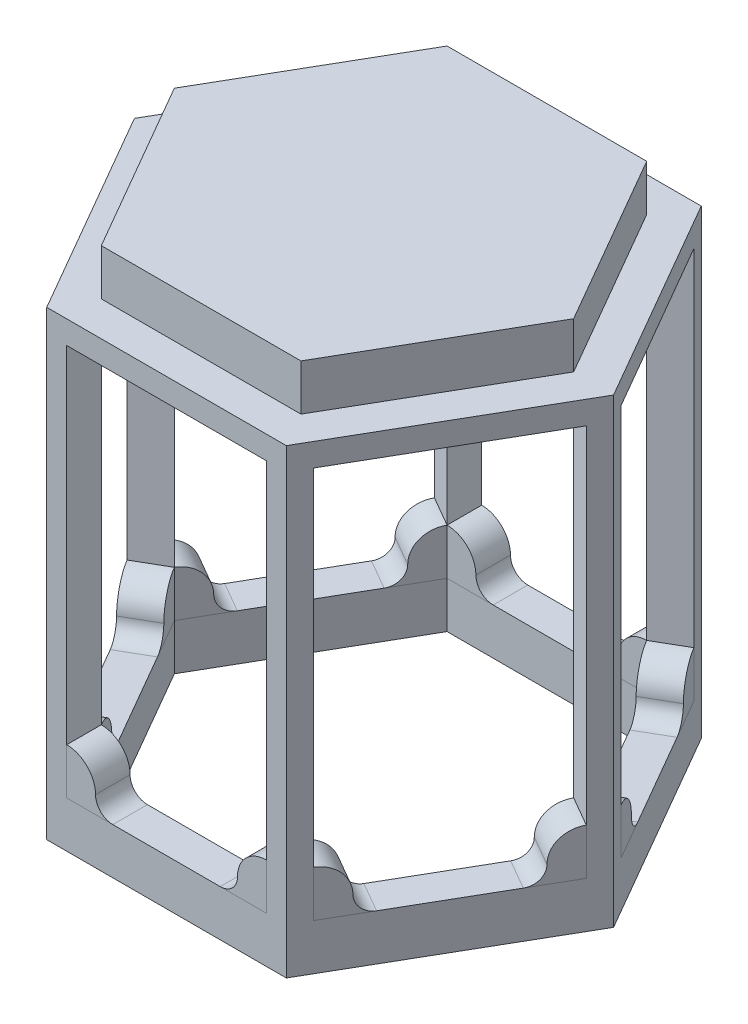
SolidWorks part; units mm, degrees
ref_plane "Front Plane" through (0, 0, 0) normal (0, 0, 1) x (1, 0, 0)
ref_plane "Top Plane" through (0, 0, 0) normal (0, 1, 0) x (1, 0, 0)
ref_plane "Right Plane" through (0, 0, 0) normal (1, 0, 0) x (0, 0, -1)
sketch "Sketch1" plane through (0, 0, 0) normal (0, 1, 0) x (1, 0, 0)
  line L1 (8.6603, 0) -> (4.3301, 7.5)
  line L2 (4.3301, 7.5) -> (-4.3301, 7.5)
  line L3 (-4.3301, 7.5) -> (-8.6603, 0)
  line L4 (-8.6603, 0) -> (-4.3301, -7.5)
  line L5 (-4.3301, -7.5) -> (4.3301, -7.5)
  line L6 (4.3301, -7.5) -> (8.6603, 0)
  line L7 (10.3923, 0) -> (5.1962, 9)
  line L8 (5.1962, 9) -> (-5.1962, 9)
  line L9 (-5.1962, 9) -> (-10.3923, 0)
  line L10 (-10.3923, 0) -> (-5.1962, -9)
  line L11 (-5.1962, -9) -> (5.1962, -9)
  line L12 (5.1962, -9) -> (10.3923, 0)
  circle A0 centre (0, 0) radius 7.5 construction
  circle A1 centre (0, 0) radius 9 construction
  dimension "D1" = 15
  dimension "D2" = 1.5
extrude "Boss-Extrude1" add sketch "Sketch1" along normal blind 2
sketch "Sketch2" plane through (0, 2, 0) normal (0, 1, 0) x (1, 0, 0)
  line L0 (-5.1962, 9) -> (-5.6292, 8.25)
  line L1 (-5.1962, 9) -> (-10.3923, 0) construction
  line L5 (-5.1962, 9) -> (-4.3301, 7.5) construction
  line L39 (-4.3301, 7.5) -> (-5.6292, 8.25)
  line L40 (-4.3301, 7.5) -> (-4.3301, 9)
  line L41 (-5.1962, 9) -> (-4.3301, 9)
  line L42 (4.3301, 7.5) -> (5.6292, 8.25)
  line L43 (5.1962, 9) -> (5.6292, 8.25)
  line L44 (5.1962, 9) -> (4.3301, 9)
  line L45 (4.3301, 7.5) -> (4.3301, 9)
  line L46 (8.6603, 0) -> (9.9593, -0.75)
  line L47 (10.3923, 0) -> (9.9593, -0.75)
  line L48 (10.3923, 0) -> (9.9593, 0.75)
  line L49 (8.6603, 0) -> (9.9593, 0.75)
  line L50 (4.3301, -7.5) -> (4.3301, -9)
  line L51 (5.1962, -9) -> (4.3301, -9)
  line L52 (5.1962, -9) -> (5.6292, -8.25)
  line L53 (4.3301, -7.5) -> (5.6292, -8.25)
  line L54 (-4.3301, -7.5) -> (-5.6292, -8.25)
  line L55 (-5.1962, -9) -> (-5.6292, -8.25)
  line L56 (-5.1962, -9) -> (-4.3301, -9)
  line L57 (-4.3301, -7.5) -> (-4.3301, -9)
  line L58 (-8.6603, 0) -> (-9.9593, 0.75)
  line L59 (-10.3923, 0) -> (-9.9593, 0.75)
  line L60 (-10.3923, 0) -> (-9.9593, -0.75)
  line L61 (-8.6603, 0) -> (-9.9593, -0.75)
  line L62 (-4.3301, 7.5) -> (-8.6603, 0) construction
  point P7 (-0.7978, -1.0505)
  point P30 (0, 0)
  dimension "D1" = 90
  dimension "D2" = 6
extrude "Boss-Extrude2" add sketch "Sketch2" along normal blind 17
sketch "Sketch3" plane through (0, 19, 0) normal (0, 1, 0) x (1, 0, 0)
  line L1 (10.3923, 0) -> (5.1962, 9)
  line L2 (5.1962, 9) -> (-5.1962, 9)
  line L3 (-5.1962, 9) -> (-10.3923, 0)
  line L4 (-10.3923, 0) -> (-5.1962, -9)
  line L5 (-5.1962, -9) -> (5.1962, -9)
  line L6 (5.1962, -9) -> (10.3923, 0)
  circle A0 centre (0, 0) radius 9 construction
  point P1 (10.3923, 0)
extrude "Boss-Extrude3" add sketch "Sketch3" along normal blind 1
sketch "Sketch4" plane through (0, 20, 0) normal (0, 1, 0) x (1, 0, 0)
  line L0 (10.3923, 0) -> (5.1962, 9) construction
  line L1 (8.6603, 0) -> (4.3301, 7.5)
  line L2 (4.3301, 7.5) -> (-4.3301, 7.5)
  line L3 (-4.3301, 7.5) -> (-8.6603, 0)
  line L4 (-8.6603, 0) -> (-4.3301, -7.5)
  line L5 (-4.3301, -7.5) -> (4.3301, -7.5)
  line L6 (4.3301, -7.5) -> (8.6603, 0)
  circle A0 centre (0, 0) radius 7.5 construction
  dimension "D1" = 1.5
extrude "Boss-Extrude4" add sketch "Sketch4" along normal blind 2
ref_axis "Axis1" through (0, 0, 0) along (0, 1, 0)
sketch "Sketch5" plane through (0, 0, -7.5) normal (0, 0, 1) x (1, 0, 0)
  line L0 (-4.3301, 2) -> (-2.3301, 2)
  line L1 (4.3301, 2) -> (-4.3301, 2) construction
  line L2 (-4.3301, 2) -> (-4.3301, 2.75)
  line L3 (-4.3301, 19) -> (-4.3301, 2) construction
  line L4 (-4.3301, 2.75) -> (-4.3301, 4)
  line L6 (0, 2) -> (0, 3.8318) construction
  line L7 (4.3301, 2) -> (4.3301, 2.75)
  line L8 (4.3301, 2.75) -> (4.3301, 4)
  line L9 (4.3301, 2) -> (2.3301, 2)
  line L10 (-4.3301, 2) -> (4.3301, 2) construction
  arc A0 (-3.0801, 2.75) -> (-4.3301, 4) centre (-4.3301, 2.75) ccw
  arc A1 (-3.0801, 2.75) -> (-2.3301, 2) centre (-2.3301, 2.75) ccw
  arc A2 (3.0801, 2.75) -> (4.3301, 4) centre (4.3301, 2.75) cw
  arc A3 (3.0801, 2.75) -> (2.3301, 2) centre (2.3301, 2.75) cw
  point P21 (-3.3301, 2.9753)
  point P22 (-3.0801, 2.7601)
  point P23 (-2.4426, 2)
  dimension "D1" = 2.5
  dimension "D4" = 0.75
  dimension "D2" = 2
  dimension "D3" = 2
extrude "Boss-Extrude12" add sketch "Sketch5" against normal up to surface (1.5 mm away) separate body up to face at (0, 10, -9)
pattern_circular "CirPattern1" count 6 over 360 about axis through (0, 0, 0) along (0, 1, 0) of bodies 106 105
